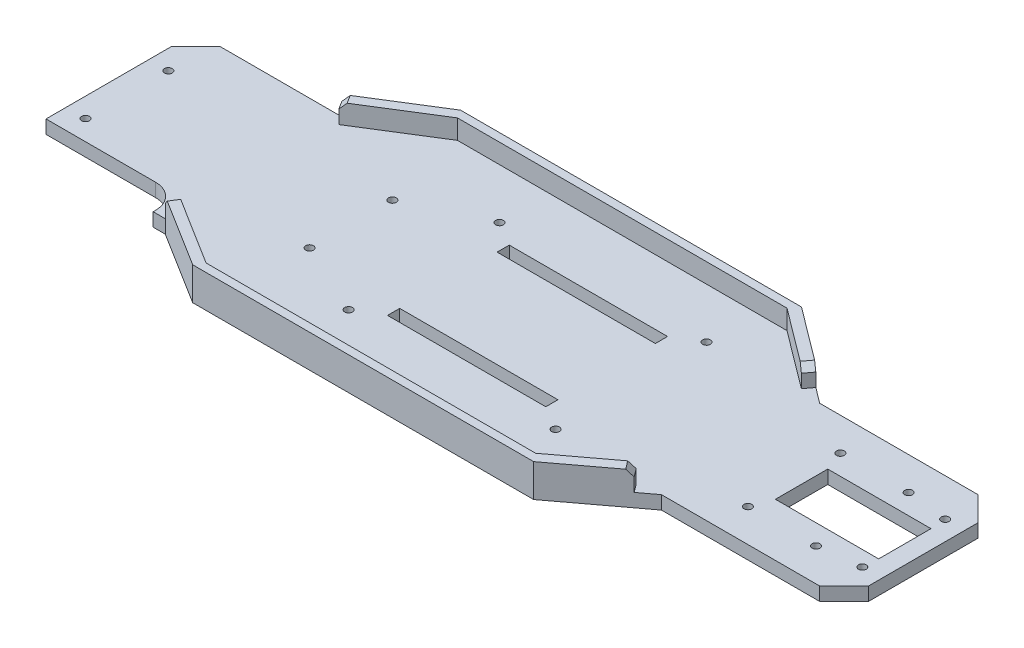
SolidWorks part; units mm, degrees
material "PETG - Polymaker"
ref_plane "Front Plane" through (0, 0, 0) normal (0, 0, 1) x (1, 0, 0)
ref_plane "Top Plane" through (0, 0, 0) normal (0, 1, 0) x (1, 0, 0)
ref_plane "Right Plane" through (0, 0, 0) normal (1, 0, 0) x (0, 0, -1)
sketch "Sketch1" plane through (0, 0, 0) normal (0, 1, 0) x (1, 0, 0)
  line L0 (-235.1499, 0) -> (235.1499, 0) construction
  line L1 (0, 0) -> (0, 52596.8311) construction
  line L2 (-100, 36.25) -> (-70, 55)
  line L3 (-70, 55) -> (70, 55)
  line L4 (-100, 36.25) -> (-160, 36.25)
  line L5 (-160, 36.25) -> (-160, -36.25)
  line L6 (-70, -55) -> (70, -55)
  line L7 (-100, -36.25) -> (-70, -55)
  line L8 (-100, -36.25) -> (-160, -36.25)
  line L9 (70, 55) -> (100, 32.5)
  line L10 (100, 32.5) -> (175, 32.5)
  line L11 (175, 32.5) -> (175, -32.5)
  line L12 (100, -32.5) -> (175, -32.5)
  line L13 (70, -55) -> (100, -32.5)
  point P3 (0, 0)
  point P10 (-85, 45.625)
  point P15 (-85, -45.625)
  point P18 (-160, 0)
  point P19 (0, -55)
  point P20 (0, 55)
  point P23 (175, 0)
  dimension "D1" = 55
  dimension "D2" = 72.5
  dimension "D3" = 30
  dimension "D4" = 60
  dimension "D5" = 140
  dimension "D6" = 75
  dimension "D7" = 65
  dimension "D8" = 30
  dimension "D9" = 110
extrude "Boss-Extrude1" add sketch "Sketch1" along normal blind 5.5
sketch "Sketch3" plane through (0, 5.5, 0) normal (0, 1, 0) x (1, 0, 0)
  line L0 (0, 0) -> (50000, 0) construction
  line L1 (0, 0) -> (0, 50000) construction
  line L2 (0, 55) -> (-70, 55)
  line L3 (70, 55) -> (-70, 55) construction
  line L4 (-70, 55) -> (-100, 36.25)
  line L5 (-100, 36.25) -> (-97.88, 32.858)
  line L6 (-97.88, 32.858) -> (-67.88, 51.608)
  line L7 (-67.88, 51.608) -> (0, 51.608)
  line L8 (-70, 55) -> (-67.88, 51.608) construction
  line L9 (0, 55) -> (70, 55)
  line L10 (70, 55) -> (93.6, 37.3)
  line L11 (93.6, 37.3) -> (91.056, 33.908)
  line L12 (91.056, 33.908) -> (67.456, 51.608)
  line L13 (67.456, 51.608) -> (0, 51.608)
  line L14 (67.456, 51.608) -> (70, 55) construction
  line L15 (67.456, -51.608) -> (70, -55) construction
  line L16 (-70, -55) -> (-67.88, -51.608) construction
  line L27 (-70, 55) -> (-100, 36.25) construction
  line L28 (100, 32.5) -> (70, 55) construction
  line L29 (67.456, -51.608) -> (0, -51.608)
  line L30 (91.056, -33.908) -> (67.456, -51.608)
  line L31 (93.6, -37.3) -> (91.056, -33.908)
  line L32 (70, -55) -> (93.6, -37.3)
  line L33 (0, -55) -> (70, -55)
  line L34 (-67.88, -51.608) -> (0, -51.608)
  line L35 (-97.88, -32.858) -> (-67.88, -51.608)
  line L36 (-100, -36.25) -> (-97.88, -32.858)
  line L37 (-70, -55) -> (-100, -36.25)
  line L38 (0, -55) -> (-70, -55)
  dimension "D1" = 4
  dimension "D2" = 0
  dimension "D3" = 8
extrude "Chassis-Walls1" add sketch "Sketch3" along normal blind 8
chamfer "Chamfer1" distance 10 angle 45 2 edges at (-160, 2.75, -36.25) (-160, 2.75, 36.25)
chamfer "Chamfer2" distance 10 angle 45 2 edges at (175, 2.75, -32.5) (175, 2.75, 32.5)
chamfer "Chamfer3" distance 2.5 angle 45 4 edges at (-98.94, 13.5, -34.554) (92.328, 13.5, -35.604) (-98.94, 13.5, 34.554) (92.328, 13.5, 35.604)
sketch "Sketch4" plane through (0, 0, 0) normal (0, -1, 0) x (1, 0, 0)
  line L0 (0, 0) -> (50000, 0) construction
  line L1 (-152, 17) -> (-60, 17) construction
  line L2 (-160, -26.25) -> (-160, 26.25) construction
  circle A0 centre (-152, 17) radius 1.6
  circle A1 centre (-60, 17) radius 1.6
  circle A2 centre (-60, -17) radius 1.6
  circle A3 centre (-152, -17) radius 1.6
  circle A4 centre (-30, 31) radius 1.6
  circle A5 centre (55, 31) radius 1.6
  circle A6 centre (55, -31) radius 1.6
  circle A7 centre (-30, -31) radius 1.6
  dimension "D1" = 3.2
  dimension "D2" = 3.2
  dimension "D6" = 3.2
  dimension "D8" = 3.2
  dimension "D3" = 8
  dimension "D4" = 92
  dimension "D5" = 34
  dimension "D7" = 30
  dimension "D9" = 85
  dimension "D10" = 62
extrude "Cut-Extrude1" cut sketch "Sketch4" against normal blind 10
sketch "Sketch5" plane through (0, 5.5, 0) normal (0, 1, 0) x (1, 0, 0)
  line L0 (-160, -25.25) -> (-105, -25.25)
  line L1 (-160, 26.25) -> (-160, -26.25) construction
  line L2 (-105, -25.25) -> (-105, -36.25)
  line L3 (-150, -36.25) -> (-100, -36.25) construction
  line L4 (-105, -36.25) -> (-160, -36.25)
  line L5 (-160, -36.25) -> (-160, -25.25)
  dimension "D1" = 55
  dimension "D2" = 11
extrude "Cut-Extrude2" cut sketch "Sketch5" against normal blind 10
sketch "Sketch6" plane through (0, 5.5, 0) normal (0, 1, 0) x (1, 0, 0)
  line L0 (0, 0) -> (50000, 0) construction
  line L1 (55, 31) -> (-30, 31) construction
  line L2 (12.5, 30.75) -> (12.5, 50030.75) construction
  line L3 (-20, -20) -> (45, -25) construction
  line L4 (-20, 25) -> (45, 25)
  line L5 (-20, 25) -> (-20, 20)
  line L6 (-20, 20) -> (45, 20)
  line L7 (45, 25) -> (45, 20)
  line L8 (-20, 25) -> (45, 20) construction
  line L9 (-20, 20) -> (45, 25) construction
  line L10 (-20, -25) -> (45, -20) construction
  line L11 (45, -25) -> (45, -20)
  line L12 (-20, -20) -> (45, -20)
  line L13 (-20, -25) -> (-20, -20)
  line L14 (-20, -25) -> (45, -25)
  point P9 (12.5, 31)
  point P10 (12.5, 22.5)
  point P19 (12.5, -22.5)
  dimension "D1" = 5
  dimension "D2" = 65
  dimension "D3" = 20
extrude "Cut-Extrude3" cut sketch "Sketch6" against normal through all
fillet "Fillet1" radius 10 1 edges at (-105, 2.75, 25.25)
sketch "Sketch7" plane through (0, 5.5, 0) normal (0, 1, 0) x (1, 0, 0)
  line L0 (175, 0) -> (50175, 0) construction
  line L1 (175, -22.5) -> (175, 22.5) construction
  line L3 (125.8, 10) -> (166.7, 10) construction
  line L4 (125.8, 10) -> (125.8, -10) construction
  line L5 (125.8, -10) -> (166.7, -10) construction
  line L6 (166.7, 10) -> (166.7, -10) construction
  line L7 (125.8, 10) -> (166.7, -10) construction
  line L8 (125.8, -10) -> (166.7, 10) construction
  line L9 (125.05, 10.75) -> (167.45, 10.75)
  line L10 (125.05, 10.75) -> (125.05, -10.75)
  line L11 (125.05, -10.75) -> (167.45, -10.75)
  line L12 (167.45, 10.75) -> (167.45, -10.75)
  line L13 (125.05, 10.75) -> (167.45, -10.75) construction
  line L14 (125.05, -10.75) -> (167.45, 10.75) construction
  point P4 (175, 0)
  point P5 (146.25, 0)
  point P10 (146.25, 0)
  dimension "D1" = 20
  dimension "D2" = 40.9
  dimension "D3" = 0.75
  dimension "D4" = 0.75
  dimension "D5" = 8.3
extrude "Cut-Extrude4" cut sketch "Sketch7" against normal through all
sketch "Sketch9" plane through (0, 5.5, 0) normal (0, 1, 0) x (1, 0, 0)
  circle A0 centre (122, -19) radius 1.6
  circle A1 centre (150, -19) radius 1.6
  circle A2 centre (167, -17) radius 1.6
  dimension "D1" = 3.2
  dimension "D2" = 3.2
  dimension "D3" = 3.2
extrude "Cut-Extrude5" cut sketch "Sketch9" against normal through all
mirror "Mirror1" about plane through (0, 0, 0) normal (0, 0, 1) of "Cut-Extrude5"
equation "\"D6@Sketch4\"=\"D2@Sketch4\""
equation "\"D8@Sketch4\"=\"D2@Sketch4\""
equation "\"D2@Sketch4\"=\"D1@Sketch4\""
equation "\"D2@Sketch9\"=\"D1@Sketch9\""
equation "\"D3@Sketch9\"=\"D1@Sketch9\""
